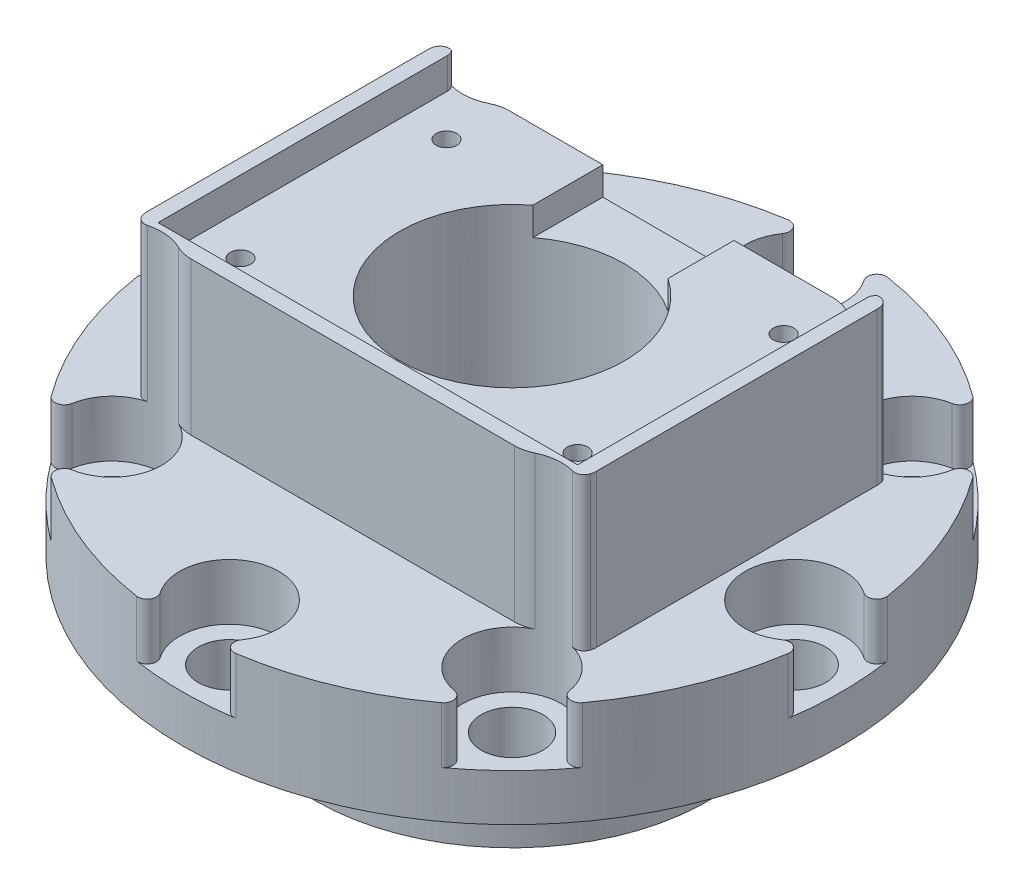
SolidWorks part; units mm, degrees
ref_plane "Front Plane" through (0, 0, 0) normal (0, 0, 1) x (1, 0, 0)
ref_plane "Top Plane" through (0, 0, 0) normal (0, 1, 0) x (1, 0, 0)
ref_plane "Right Plane" through (0, 0, 0) normal (1, 0, 0) x (0, 0, -1)
ref_plane "Plane1" through (0, 18.1, 0) normal (0, -1, 0) x (-1, 0, 0)
ref_plane "Plane2" through (0, 6.1, 0) normal (0, 1, 0) x (1, 0, 0)
sketch "Sketch1" plane through (0, 18.1, 0) normal (0, -1, 0) x (-1, 0, 0)
  line L0 (-10, 18.7) -> (10, 18.7) construction
  line L1 (-10, 18.7) -> (-10, 13.7) construction
  line L2 (10, 18.7) -> (10, 13.7) construction
  line L3 (-10, 13.7) -> (10, 13.7) construction
  line L4 (11, -7.5) -> (11, 20.5)
  line L5 (11, 20.5) -> (-11, 20.5)
  line L6 (5.2, 11.5) -> (-3.35, 11.5)
  line L7 (-3.35, 11.5) -> (-3.35, 4.5)
  line L8 (-3.35, 4.5) -> (3.65, 4.5)
  line L9 (3.65, 4.5) -> (3.65, 9)
  line L10 (3.65, 9) -> (5.2, 9)
  line L11 (5.2, 9) -> (5.2, 11.5)
  line L12 (5.2, 11.5) -> (-3.35, 11.5)
  line L13 (-3.35, 11.5) -> (-3.35, 4.5)
  line L14 (-3.35, 4.5) -> (3.65, 4.5)
  line L15 (3.65, 4.5) -> (3.65, 9)
  line L16 (3.65, 9) -> (5.2, 9)
  line L17 (5.2, 9) -> (5.2, 11.5)
  line L18 (-11, 20.5) -> (-11, -7.5)
  line L19 (-11, -7.5) -> (11, -7.5)
  line L20 (11, -7.5) -> (11, 20.5)
  line L21 (11, 20.5) -> (-11, 20.5)
  line L22 (-11, 20.5) -> (-11, -7.5)
  line L23 (-11, -7.5) -> (11, -7.5)
  line L24 (-2.58, -2.15) -> (2.58, -2.15)
  line L25 (-2.58, 2.15) -> (-2.58, -2.15)
  line L26 (2.58, 2.15) -> (-2.58, 2.15)
  line L27 (2.58, -2.15) -> (2.58, 2.15)
  line L28 (-2.58, -2.15) -> (2.58, -2.15)
  line L29 (-2.58, 2.15) -> (-2.58, -2.15)
  line L30 (2.58, 2.15) -> (-2.58, 2.15)
  line L31 (2.58, -2.15) -> (2.58, 2.15)
  line L32 (-10, 18.7) -> (10, 18.7)
  line L33 (-10, 18.7) -> (-10, 13.7)
  line L34 (10, 18.7) -> (10, 13.7)
  line L35 (-10, 13.7) -> (10, 13.7)
  circle A0 centre (-9, 5.5) radius 1.3 construction
  circle A1 centre (-9, -5.5) radius 1.3 construction
  circle A2 centre (9, -5.5) radius 1.3 construction
  circle A3 centre (9, 5.5) radius 1.3 construction
  circle A4 centre (-9, 5.5) radius 1.3
  circle A5 centre (-9, -5.5) radius 1.3
  circle A6 centre (9, -5.5) radius 1.3
  circle A7 centre (9, 5.5) radius 1.3
  dimension "D1" = 0
  dimension "D2" = 0
  dimension "D3" = 0
sketch "Sketch2" plane through (0, 6.1, 0) normal (0, 1, 0) x (1, 0, 0)
  line L0 (0, -12.6) -> (0, -17.6) construction
  arc A0 (-17.6, 0) -> (17.6, 0) centre (0, 0) ccw construction
  arc A1 (-17.6, 0) -> (17.6, 0) centre (0, 0) ccw construction
  circle A2 centre (0, 0) radius 12.6 construction
  circle A3 centre (0, 0) radius 12.6 construction
  circle A4 centre (0, 0) radius 17.6
  circle A5 centre (0, 0) radius 6
  circle A6 centre (0, -15.1) radius 1.65
  circle A7 centre (0, -15.1) radius 1.65 construction
  circle A8 centre (-10.6773, -10.6773) radius 1.65
  circle A9 centre (-15.1, 0) radius 1.65
  circle A10 centre (-10.6773, 10.6773) radius 1.65
  circle A11 centre (0, 15.1) radius 1.65
  circle A12 centre (10.6773, 10.6773) radius 1.65
  circle A13 centre (15.1, 0) radius 1.65
  circle A14 centre (10.6773, -10.6773) radius 1.65
  dimension "D1" = 12
sketch "Sketch3" plane through (0, 0, 0) normal (0, 1, 0) x (1, 0, 0)
  circle A0 centre (0, 0) radius 8.49
  circle A1 centre (0, 0) radius 8.49 construction
  circle A2 centre (0, 0) radius 10.49
  dimension "D1" = 2
extrude "Boss-Extrude1" add sketch "Sketch2" along normal blind 2.5
extrude "Boss-Extrude2" add sketch "Sketch3" along normal up to surface (6.1 mm away) up to face at (0, 6.1, 17.6)
sketch "Sketch4" plane through (0, 8.6, 0) normal (0, 1, 0) x (1, 0, 0)
  circle A0 centre (0, 0) radius 12.6 construction
  circle A1 centre (0, 0) radius 12.6
sketch "Sketch5" plane through (0, 18.1, 0) normal (0, -1, 0) x (-1, 0, 0)
  line L0 (11, -7.5) -> (11, 20.5) construction
  line L1 (-11, 20.5) -> (-11, -7.5) construction
  line L2 (-11, -7.5) -> (11, -7.5) construction
  line L3 (11, -7.5) -> (11, 20.5) construction
  line L4 (-11, 20.5) -> (-11, -7.5) construction
  line L5 (-11, -7.5) -> (11, -7.5) construction
  line L6 (-12, 7.5) -> (-12, -7.5)
  line L7 (-11, -8.5) -> (11, -8.5)
  line L8 (12, -7.5) -> (12, 7.5)
  line L9 (-12, -8.5) -> (12, -8.5) construction
  line L10 (12, -8.5) -> (12, 20.5) construction
  line L11 (-12, 20.5) -> (-12, -8.5) construction
  line L12 (11, 8.5) -> (-11, 8.5)
  line L13 (9, -6.8) -> (9, -8.5) construction
  line L14 (9, 6.8) -> (9, 8.5) construction
  circle A0 centre (9, -5.5) radius 1.3 construction
  circle A1 centre (0, 0) radius 12.6
  circle A2 centre (0, 0) radius 12.6 construction
  circle A3 centre (9, 5.5) radius 1.3 construction
  circle A4 centre (-9, -5.5) radius 1.3 construction
  circle A5 centre (-9, 5.5) radius 1.3 construction
  circle A6 centre (9, -5.5) radius 1.3 construction
  circle A7 centre (9, 5.5) radius 1.3 construction
  circle A8 centre (-9, -5.5) radius 1.3 construction
  circle A9 centre (-9, 5.5) radius 1.3 construction
  arc A10 (11, -8.5) -> (12, -7.5) centre (11, -7.5) ccw
  arc A11 (-11, -8.5) -> (-12, -7.5) centre (-11, -7.5) cw
  circle A13 centre (0, 0) radius 6 construction
  circle A14 centre (0, 0) radius 6
  arc A15 (12, 7.5) -> (11, 8.5) centre (11, 7.5) ccw
  arc A16 (-11, 8.5) -> (-12, 7.5) centre (-11, 7.5) ccw
  point P23 (-12, 6.8)
  point P24 (12, 5.6167)
  point P25 (0, 8.5)
  point P33 (0, 0)
  point P43 (11.7634, 8.5)
  point P44 (13.5799, 8.5)
  point P45 (-12.0969, 4.1989)
  point P46 (0, 0)
  point P47 (0, 0)
  point P48 (12.2698, 5.1218)
  point P49 (0, 0)
  dimension "D3" = 1
  dimension "D4" = 1
  dimension "D1" = 0
  dimension "D2" = 1
extrude "Boss-Extrude3" add sketch "Sketch5" along normal up to surface (9.5 mm away) up to face at (15.1, 8.6, 1.65)
sketch "Sketch6" plane through (0, 18.1, 0) normal (0, 1, 0) x (1, 0, 0)
  line L0 (11, -7.5) -> (-11, -7.5) construction
  line L1 (-11, -7.5) -> (-11, 20.5) construction
  line L2 (11, 20.5) -> (11, -7.5) construction
  line L3 (11, -7.5) -> (-11, -7.5) construction
  line L4 (11, 8.5) -> (-11, 8.5)
  line L5 (-12, 7.5) -> (-12, -7.5)
  line L6 (-11, -8.5) -> (11, -8.5)
  line L7 (12, -7.5) -> (12, 7.5)
  line L9 (-12, 7.5) -> (-12, -7.5)
  line L10 (-11, -8.5) -> (11, -8.5)
  line L11 (12, -7.5) -> (12, 7.5)
  line L12 (-11, -7.5) -> (-11, 20.5) construction
  line L13 (11, 20.5) -> (11, -7.5) construction
  line L14 (11.2, 8.4798) -> (11.2, -7.7)
  line L15 (11.2, -7.7) -> (-11.2, -7.7)
  line L16 (-11.2, -7.7) -> (-11.2, 8.4798)
  line L17 (11.2, 20.5) -> (11.2, -7.7) construction
  line L18 (-11.2, -7.7) -> (-11.2, 20.5) construction
  arc A6 (12, 7.5) -> (11, 8.5) centre (11, 7.5) ccw
  arc A7 (-11, 8.5) -> (-12, 7.5) centre (-11, 7.5) ccw
  arc A8 (-12, -7.5) -> (-11, -8.5) centre (-11, -7.5) ccw
  arc A9 (11, -8.5) -> (12, -7.5) centre (11, -7.5) ccw
  arc A10 (12, 7.5) -> (11.2, 8.4798) centre (11, 7.5) ccw
  arc A11 (-11.2, 8.4798) -> (-12, 7.5) centre (-11, 7.5) ccw
  arc A12 (-12, -7.5) -> (-11, -8.5) centre (-11, -7.5) ccw
  arc A13 (11, -8.5) -> (12, -7.5) centre (11, -7.5) ccw
  dimension "D2" = 0
  dimension "D3" = 0.2
extrude "Boss-Extrude4" add sketch "Sketch6" along normal blind 1.65
sketch "Sketch7" plane through (0, 8.6, 0) normal (0, 1, 0) x (1, 0, 0)
  circle A0 centre (10.6773, 10.6773) radius 2.65
  circle A1 centre (-10.6773, 10.6773) radius 2.65
  circle A2 centre (-10.6773, -10.6773) radius 2.65
  circle A3 centre (10.6773, -10.6773) radius 2.65
  dimension "D1" = 5.3
extrude "Cut-Extrude1" cut sketch "Sketch7" along normal through all
sketch "Sketch8" plane through (0, 8.6, 0) normal (0, 1, 0) x (1, 0, 0)
  circle A0 centre (0, 0) radius 17.6 construction
  arc A1 (0.9485, -17.5744) -> (11.7563, -13.0977) centre (0, 0) ccw
  arc A2 (-0.9485, 17.5744) -> (0.9485, 17.5744) centre (0, 15.1) ccw
  circle A3 centre (10.6773, -10.6773) radius 2.65
  arc A4 (13.0977, -11.7563) -> (11.7563, -13.0977) centre (10.6773, -10.6773) ccw
  circle A5 centre (-10.6773, -10.6773) radius 2.65
  arc A6 (-11.7563, -13.0977) -> (-13.0977, -11.7563) centre (-10.6773, -10.6773) ccw
  circle A7 centre (-10.6773, 10.6773) radius 2.65
  arc A8 (-13.0977, 11.7563) -> (-11.7563, 13.0977) centre (-10.6773, 10.6773) ccw
  circle A9 centre (10.6773, 10.6773) radius 2.65
  arc A10 (11.7563, 13.0977) -> (13.0977, 11.7563) centre (10.6773, 10.6773) ccw
  arc A11 (-17.5744, -0.9485) -> (-17.5744, 0.9485) centre (-15.1, 0) ccw
  arc A12 (0.9485, -17.5744) -> (-0.9485, -17.5744) centre (0, -15.1) ccw
  arc A13 (17.5744, 0.9485) -> (17.5744, -0.9485) centre (15.1, 0) ccw
  arc A14 (13.0977, -11.7563) -> (17.5744, -0.9485) centre (0, 0) ccw
  arc A15 (17.5744, 0.9485) -> (13.0977, 11.7563) centre (0, 0) ccw
  arc A16 (11.7563, 13.0977) -> (0.9485, 17.5744) centre (0, 0) ccw
  arc A17 (-0.9485, 17.5744) -> (-11.7563, 13.0977) centre (0, 0) ccw
  arc A18 (-13.0977, 11.7563) -> (-17.5744, 0.9485) centre (0, 0) ccw
  arc A19 (-17.5744, -0.9485) -> (-13.0977, -11.7563) centre (0, 0) ccw
  arc A20 (-11.7563, -13.0977) -> (-0.9485, -17.5744) centre (0, 0) ccw
  circle A21 centre (0, 0) radius 6 construction
  circle A22 centre (0, 0) radius 6
  dimension "D1" = 0
  dimension "D2" = 0
  dimension "D3" = 0
  dimension "D4" = 0
extrude "Boss-Extrude5" add sketch "Sketch8" along normal blind 3
fillet "Fillet2" radius 0.5 20 edges at (11.6866, 15.675, 8.227) (-11.6866, 15.675, 8.227) (-11.6866, 15.675, -8.227) (11.6866, 15.675, -8.227) (17.5744, 10.1, -0.9485) (-13.0977, 10.1, 11.7563) (11.7563, 10.1, -13.0977) (0.9485, 10.1, -17.5744) (-0.9485, 10.1, -17.5744) (-11.7563, 10.1, -13.0977) (-13.0977, 10.1, -11.7563) (-17.5744, 10.1, -0.9485) (-17.5744, 10.1, 0.9485) (-11.7563, 10.1, 13.0977) (-0.9485, 10.1, 17.5744) (0.9485, 10.1, 17.5744) (13.0977, 10.1, 11.7563) (11.7563, 10.1, 13.0977) (17.5744, 10.1, 0.9485) (13.0977, 10.1, -11.7563)
fillet "Fillet3" radius 0.5 2 edges at (-11.2, 18.925, -8.0794) (11.2, 18.925, -8.0794)
fillet "Fillet4" radius 2 4 edges at (9.1667, 15.675, 8.5) (-9.1667, 15.675, 8.5) (-9.1667, 14.85, -8.5) (9.1667, 14.85, -8.5)
chamfer "Chamfer1" distance 0.5 angle 45 1 edges at (0, 0, 8.49)
sketch "Sketch9" plane through (0, 18.1, 0) normal (0, 1, 0) x (1, 0, 0)
  circle A0 centre (9, -5.5) radius 0.55
  circle A1 centre (-9, -5.5) radius 0.55
  circle A2 centre (-9, 5.5) radius 0.55
  circle A3 centre (9, 5.5) radius 0.55
  dimension "D1" = 1.1
extrude "Cut-Extrude2" cut sketch "Sketch9" against normal blind 5
sketch "Sketch10" plane through (0, 6.1, 0) normal (0, -1, 0) x (1, 0, 0)
  circle A1 centre (0, 0) radius 8.49
  circle A2 centre (0, 0) radius 8.49
  dimension "D1" = 0
extrude "Cut-Extrude4" cut sketch "Sketch10" against normal blind 0.3
sketch "Sketch11" plane through (0, 18.1, 0) normal (0, 1, 0) x (1, 0, 0)
  line L0 (-5.2, 9) -> (-5.2, 11.5) construction
  line L1 (-3.65, 9) -> (-5.2, 9) construction
  line L2 (3.35, 11.5) -> (3.35, 4.5) construction
  line L3 (3.35, 4.5) -> (-3.65, 4.5) construction
  line L4 (-3.65, 4.5) -> (-3.65, 9) construction
  line L5 (-5.2, 11.5) -> (3.35, 11.5) construction
  line L6 (-5.2, 9) -> (-5.2, 11.5)
  line L7 (-3.65, 9) -> (-5.2, 9)
  line L8 (3.35, 11.5) -> (3.35, 4.5)
  line L9 (3.35, 4.5) -> (-3.65, 4.5)
  line L10 (-3.65, 4.5) -> (-3.65, 9)
  line L11 (-5.2, 11.5) -> (3.35, 11.5)
extrude "Cut-Extrude5" cut sketch "Sketch11" against normal blind 1.5
